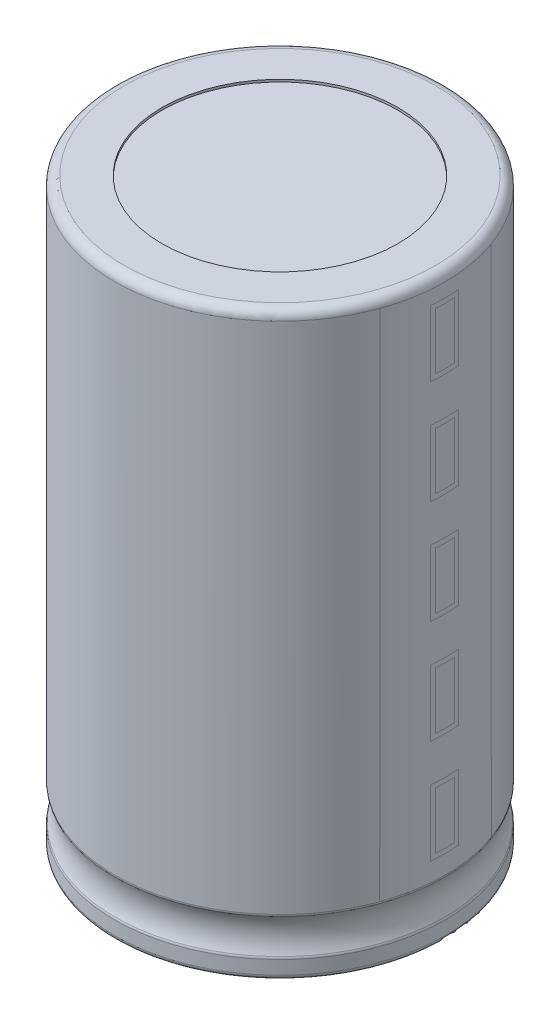
SolidWorks part; units mm, degrees
ref_plane "Спереди" through (0, 0, 0) normal (0, 0, 1) x (1, 0, 0)
ref_plane "Сверху" through (0, 0, 0) normal (0, 1, 0) x (1, 0, 0)
ref_plane "Справа" through (0, 0, 0) normal (1, 0, 0) x (0, 0, -1)
sketch "Эскиз1" plane through (0, 0, 0) normal (1, 0, 0) x (0, 0, -1)
  line L0 (12.5, 0) -> (17, 0)
  line L1 (17.5, 0.5) -> (17.5, 1.9384)
  line L2 (16.5, 61.5) -> (12.5, 61.5)
  line L3 (0, -15.5058) -> (0, 78.5193) construction
  line L5 (21, 4) -> (0, 4) construction
  line L6 (17.5, 6.0616) -> (17.5, 60.5)
  line L9 (12.5, 61.5) -> (12.5, 61.25)
  line L10 (12.5, 61.25) -> (0, 61.25)
  line L11 (0, 61.25) -> (0, 1)
  line L12 (12.5, 0.25) -> (14, 0.25)
  line L13 (12.5, 0.25) -> (12.5, 0)
  line L14 (0, 1) -> (14, 1)
  line L15 (14, 1) -> (14, 0.25)
  arc A2 (17.5, 0.5) -> (17, 0) centre (17, 0.5) cw
  arc A3 (17.4444, 5.8325) -> (17.4444, 2.1675) centre (21, 4) ccw
  arc A4 (17.5, 60.5) -> (16.5, 61.5) centre (16.5, 60.5) ccw
  arc A5 (17.4444, 2.1675) -> (17.5, 1.9384) centre (17, 1.9384) cw
  arc A6 (17.5, 6.0616) -> (17.4444, 5.8325) centre (17, 6.0616) cw
  point P3 (17.5, 61.5)
  point P7 (0, 0)
  point P8 (0, 0)
  point P10 (17.5, 62)
  point P11 (17.4602, 62)
  point P14 (17.5, 61.5)
  point P17 (17.5, 0)
  point P32 (17.5, 5.9365)
  dimension "D3" = 1
  dimension "D4" = 0.5
  dimension "D8" = 4
  dimension "D5" = 0.5
  dimension "D2" = 61.5
  dimension "D6" = 21
  dimension "D7" = 12.5
  dimension "D9" = 0.25
  dimension "D10" = 14
  dimension "D11" = 4
  dimension "D12" = 17.5
  dimension "D13" = 12.5
  dimension "D14" = 0.25
  dimension "D15" = 1
  dimension "D16" = 1.5
revolve "Повернуть1" add sketch "Эскиз1" angle 360 about L3
sketch "Эскиз2" plane through (0, 0, 0) normal (1, 0, 0) x (0, 0, -1)
  line L0 (0, -1000) -> (0, 49000) construction
  line L12 (-6, 60.5) -> (6, 60.5)
  line L22 (-6, 60.5) -> (-6, 6.0616)
  line L27 (-6, 6.0616) -> (6, 6.0616)
  line L30 (6, 60.5) -> (6, 6.0616)
  line L31 (-6, 60.5) -> (6, 6.0616) construction
  line L32 (-6, 6.0616) -> (6, 60.5) construction
  line L33 (17.5, 60.5) -> (-17.5, 60.5) construction
  line L34 (17.5, 6.0616) -> (-17.5, 6.0616) construction
  point P1 (0, 33.2808)
  point P8 (0, 6.0616)
  point P11 (0, 60.5)
  point P14 (0, 33.2808)
  dimension "D1" = 12
  dimension "D6" = 33.2808
wrap "Перенос1" sketch "Эскиз2" wrap type scribe source sketch "Эскиз2" face at (0, 60.5, -17.5)
sketch "Эскиз4" plane through (0, 0, 0) normal (1, 0, 0) x (0, 0, -1)
  line L0 (0, -1000) -> (0, 49000) construction
  line L2 (1, 36.5308) -> (-1, 36.5308)
  line L3 (1, 36.5308) -> (1, 30.5308)
  line L4 (1, 30.5308) -> (-1, 30.5308)
  line L5 (-1, 36.5308) -> (-1, 30.5308)
  line L6 (1, 36.5308) -> (-1, 30.5308) construction
  line L7 (1, 30.5308) -> (-1, 36.5308) construction
  line L15 (-1000, 33.5308) -> (49000, 33.5308) construction
  line L24 (-1.5, 48.0308) -> (-1.5, 41.0308)
  line L25 (-1.5, 37.0308) -> (1.5, 37.0308)
  line L26 (-1.5, 37.0308) -> (-1.5, 30.0308)
  line L27 (-1.5, 30.0308) -> (1.5, 30.0308)
  line L28 (1.5, 37.0308) -> (1.5, 30.0308)
  line L29 (-1.5, 37.0308) -> (1.5, 30.0308) construction
  line L30 (-1.5, 30.0308) -> (1.5, 37.0308) construction
  line L31 (-1.5, 48.0308) -> (1.5, 48.0308)
  line L32 (1.5, 48.0308) -> (1.5, 41.0308)
  line L33 (-1.5, 41.0308) -> (1.5, 41.0308)
  line L34 (1, 47.5308) -> (1, 41.5308)
  line L35 (1, 47.5308) -> (-1, 47.5308)
  line L36 (-1, 47.5308) -> (-1, 41.5308)
  line L37 (1, 41.5308) -> (-1, 41.5308)
  line L38 (-1.5, 59.0308) -> (-1.5, 52.0308)
  line L39 (-1.5, 59.0308) -> (1.5, 59.0308)
  line L40 (1.5, 59.0308) -> (1.5, 52.0308)
  line L41 (-1.5, 52.0308) -> (1.5, 52.0308)
  line L42 (1, 58.5308) -> (1, 52.5308)
  line L43 (1, 58.5308) -> (-1, 58.5308)
  line L44 (-1, 58.5308) -> (-1, 52.5308)
  line L45 (1, 52.5308) -> (-1, 52.5308)
  line L46 (1, 14.5308) -> (-1, 14.5308)
  line L47 (-1, 8.5308) -> (-1, 14.5308)
  line L48 (1, 8.5308) -> (-1, 8.5308)
  line L49 (1, 8.5308) -> (1, 14.5308)
  line L50 (-1.5, 15.0308) -> (1.5, 15.0308)
  line L51 (1.5, 8.0308) -> (1.5, 15.0308)
  line L52 (-1.5, 8.0308) -> (1.5, 8.0308)
  line L53 (-1.5, 8.0308) -> (-1.5, 15.0308)
  line L54 (1, 25.5308) -> (-1, 25.5308)
  line L55 (-1, 19.5308) -> (-1, 25.5308)
  line L56 (1, 19.5308) -> (-1, 19.5308)
  line L57 (1, 19.5308) -> (1, 25.5308)
  line L58 (-1.5, 26.0308) -> (1.5, 26.0308)
  line L59 (1.5, 19.0308) -> (1.5, 26.0308)
  line L60 (-1.5, 19.0308) -> (1.5, 19.0308)
  line L61 (-1.5, 19.0308) -> (-1.5, 26.0308)
  point P1 (0, 33.5308)
  point P26 (0, 33.5308)
  dimension "D1" = 33.5308
  dimension "D2" = 6
  dimension "D3" = 2
  dimension "D5" = 7
  dimension "D6" = 3
  dimension "D4" = 3
wrap "Перенос3" sketch "Эскиз4" wrap type scribe source sketch "Эскиз4" face at (0, 60.5, -17.5)
sketch "Эскиз5" plane through (0, 1, 0) normal (0, -1, 0) x (1, 0, 0)
  line L0 (0, -17.5) -> (0, 17.5) construction
  line L1 (17.5, 0) -> (-17.5, 0) construction
  line L2 (5.8, -0.4) -> (4.2, 0.4) construction
  line L3 (-5.8, 0.4) -> (-4.2, 0.4)
  line L4 (-5.8, 0.4) -> (-5.8, -0.4)
  line L5 (-5.8, -0.4) -> (-4.2, -0.4)
  line L6 (-4.2, 0.4) -> (-4.2, -0.4)
  line L7 (-5.8, 0.4) -> (-4.2, -0.4) construction
  line L8 (-5.8, -0.4) -> (-4.2, 0.4) construction
  line L9 (5.8, 0.4) -> (4.2, -0.4) construction
  line L10 (4.2, 0.4) -> (4.2, -0.4)
  line L11 (5.8, -0.4) -> (4.2, -0.4)
  line L12 (5.8, 0.4) -> (5.8, -0.4)
  line L13 (5.8, 0.4) -> (4.2, 0.4)
  point P0 (-5, 0)
  point P6 (0, 0)
  point P10 (0, 0)
  point P19 (5, 0)
  dimension "D1" = 0.8
  dimension "D2" = 1.6
  dimension "D3" = 10
extrude "Бобышка-Вытянуть1" add sketch "Эскиз5" along normal blind 6
fillet "Скругление1" radius 0.25 8 edges at (4.2, -2, 0.4) (-4.2, -2, 0.4) (-4.2, -2, -0.4) (5.8, -2, 0.4) (5.8, -2, -0.4) (4.2, -2, -0.4) (-5.8, -2, -0.4) (-5.8, -2, 0.4)
chamfer "Фаска1" distance 0.25 angle 45 16 edges at (-4.2732, -5, -0.3268) (-5, -5, -0.4) (-5.7268, -5, -0.3268) (-5.8, -5, 0) (-5.7268, -5, 0.3268) (-5, -5, 0.4) (-4.2732, -5, 0.3268) (-4.2, -5, 0) (5.7268, -5, 0.3268) (5.8, -5, 0) (5.7268, -5, -0.3268) (5, -5, -0.4) (4.2732, -5, -0.3268) (4.2, -5, 0) (4.2732, -5, 0.3268) (5, -5, 0.4)
